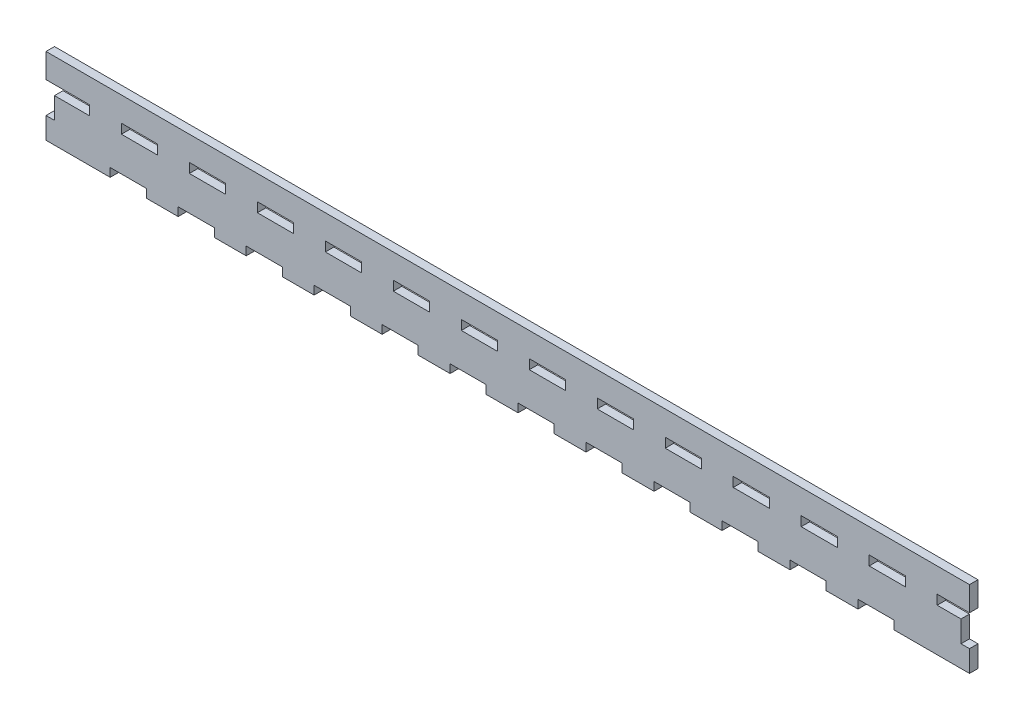
SolidWorks part; units mm, degrees
ref_plane "Plan de face" through (0, 0, 0) normal (0, 0, 1) x (1, 0, 0)
ref_plane "Plan de dessus" through (0, 0, 0) normal (0, 1, 0) x (1, 0, 0)
ref_plane "Plan de droite" through (0, 0, 0) normal (1, 0, 0) x (0, 0, -1)
sketch "Esquisse1" plane through (0, 0, 0) normal (0, 0, 1) x (1, 0, 0)
  line L6 (108.68, -6.055) -> (-108.68, -6.055)
  line L8 (108.68, -6.055) -> (108.68, 6.055)
  line L9 (108.68, 6.055) -> (-108.68, 6.055)
  line L10 (-108.68, -6.055) -> (-108.68, 6.055)
  point P4 (0, 0)
  point P5 (-108.8995, 6.2992)
extrude "Boss.-Extru.1" add sketch "Esquisse1" along normal blind 2
sketch "Esquisse2" plane through (0, 0, 0) normal (0, 0, -1) x (-1, 0, 0)
  line L0 (-108.68, 6.055) -> (-101.32, 6.055) construction
  line L1 (-109.57, 4.055) -> (-101.07, 4.055)
  line L2 (-109.57, 4.055) -> (-109.57, 6.305)
  line L3 (-109.57, 6.305) -> (-101.07, 6.305)
  line L4 (-101.07, 4.055) -> (-101.07, 6.305)
  line L9 (-93.32, 4.055) -> (-93.32, 6.055) construction
  line L10 (-101.32, 6.055) -> (-101.32, 4.055) construction
  line L12 (-85.07, 4.055) -> (-85.07, 6.305)
  line L13 (-93.57, 6.305) -> (-85.07, 6.305)
  line L14 (-93.57, 4.055) -> (-93.57, 6.305)
  line L15 (-93.57, 4.055) -> (-85.07, 4.055)
  line L16 (-69.07, 4.055) -> (-69.07, 6.305)
  line L17 (-77.57, 6.305) -> (-69.07, 6.305)
  line L18 (-77.57, 4.055) -> (-77.57, 6.305)
  line L19 (-77.57, 4.055) -> (-69.07, 4.055)
  line L20 (-53.07, 4.055) -> (-53.07, 6.305)
  line L21 (-61.57, 6.305) -> (-53.07, 6.305)
  line L22 (-61.57, 4.055) -> (-61.57, 6.305)
  line L23 (-61.57, 4.055) -> (-53.07, 4.055)
  line L24 (-37.07, 4.055) -> (-37.07, 6.305)
  line L25 (-45.57, 6.305) -> (-37.07, 6.305)
  line L26 (-45.57, 4.055) -> (-45.57, 6.305)
  line L27 (-45.57, 4.055) -> (-37.07, 4.055)
  line L28 (-21.07, 4.055) -> (-21.07, 6.305)
  line L29 (-29.57, 6.305) -> (-21.07, 6.305)
  line L30 (-29.57, 4.055) -> (-29.57, 6.305)
  line L31 (-29.57, 4.055) -> (-21.07, 4.055)
  line L32 (-5.07, 4.055) -> (-5.07, 6.305)
  line L33 (-13.57, 6.305) -> (-5.07, 6.305)
  line L34 (-13.57, 4.055) -> (-13.57, 6.305)
  line L35 (-13.57, 4.055) -> (-5.07, 4.055)
  line L36 (10.93, 4.055) -> (10.93, 6.305)
  line L37 (2.43, 6.305) -> (10.93, 6.305)
  line L38 (2.43, 4.055) -> (2.43, 6.305)
  line L39 (2.43, 4.055) -> (10.93, 4.055)
  line L40 (26.93, 4.055) -> (26.93, 6.305)
  line L41 (18.43, 6.305) -> (26.93, 6.305)
  line L42 (18.43, 4.055) -> (18.43, 6.305)
  line L43 (18.43, 4.055) -> (26.93, 4.055)
  line L44 (42.93, 4.055) -> (42.93, 6.305)
  line L45 (34.43, 6.305) -> (42.93, 6.305)
  line L46 (34.43, 4.055) -> (34.43, 6.305)
  line L47 (34.43, 4.055) -> (42.93, 4.055)
  line L48 (58.93, 4.055) -> (58.93, 6.305)
  line L49 (50.43, 6.305) -> (58.93, 6.305)
  line L50 (50.43, 4.055) -> (50.43, 6.305)
  line L51 (50.43, 4.055) -> (58.93, 4.055)
  line L52 (74.93, 4.055) -> (74.93, 6.305)
  line L53 (66.43, 6.305) -> (74.93, 6.305)
  line L54 (66.43, 4.055) -> (66.43, 6.305)
  line L55 (66.43, 4.055) -> (74.93, 4.055)
  line L56 (90.93, 4.055) -> (90.93, 6.305)
  line L57 (82.43, 6.305) -> (90.93, 6.305)
  line L58 (82.43, 4.055) -> (82.43, 6.305)
  line L59 (82.43, 4.055) -> (90.93, 4.055)
  line L60 (90.68, 6.055) -> (90.68, 4.055) construction
  line L61 (98.68, 4.055) -> (98.68, 6.055) construction
  line L62 (98.43, 4.055) -> (108.93, 4.055)
  line L63 (98.43, 4.055) -> (98.43, 6.305)
  line L64 (98.43, 6.305) -> (108.93, 6.305)
  line L65 (108.93, 4.055) -> (108.93, 6.305)
  line L66 (108.68, 6.055) -> (108.68, -6.055) construction
  line L68 (108.68, 6.055) -> (98.68, 6.055) construction
  line L70 (-90.93, -4.055) -> (-82.43, -4.055)
  line L71 (-90.93, -4.055) -> (-90.93, -6.305)
  line L72 (-90.93, -6.305) -> (-82.43, -6.305)
  line L73 (-82.43, -4.055) -> (-82.43, -6.305)
  line L74 (-90.68, -6.055) -> (-90.68, -4.055) construction
  line L75 (-90.68, -6.055) -> (-82.68, -6.055) construction
  line L76 (-82.68, -6.055) -> (-82.68, -4.055) construction
  line L77 (-74.93, -4.055) -> (-74.93, -6.305)
  line L78 (-74.93, -4.055) -> (-66.43, -4.055)
  line L79 (-66.43, -4.055) -> (-66.43, -6.305)
  line L80 (-74.93, -6.305) -> (-66.43, -6.305)
  line L81 (-58.93, -4.055) -> (-58.93, -6.305)
  line L82 (-58.93, -4.055) -> (-50.43, -4.055)
  line L83 (-50.43, -4.055) -> (-50.43, -6.305)
  line L84 (-58.93, -6.305) -> (-50.43, -6.305)
  line L85 (-42.93, -4.055) -> (-42.93, -6.305)
  line L86 (-42.93, -4.055) -> (-34.43, -4.055)
  line L87 (-34.43, -4.055) -> (-34.43, -6.305)
  line L88 (-42.93, -6.305) -> (-34.43, -6.305)
  line L89 (-26.93, -4.055) -> (-26.93, -6.305)
  line L90 (-26.93, -4.055) -> (-18.43, -4.055)
  line L91 (-18.43, -4.055) -> (-18.43, -6.305)
  line L92 (-26.93, -6.305) -> (-18.43, -6.305)
  line L93 (-10.93, -4.055) -> (-10.93, -6.305)
  line L94 (-10.93, -4.055) -> (-2.43, -4.055)
  line L95 (-2.43, -4.055) -> (-2.43, -6.305)
  line L96 (-10.93, -6.305) -> (-2.43, -6.305)
  line L97 (5.07, -4.055) -> (5.07, -6.305)
  line L98 (5.07, -4.055) -> (13.57, -4.055)
  line L99 (13.57, -4.055) -> (13.57, -6.305)
  line L100 (5.07, -6.305) -> (13.57, -6.305)
  line L101 (21.07, -4.055) -> (21.07, -6.305)
  line L102 (21.07, -4.055) -> (29.57, -4.055)
  line L103 (29.57, -4.055) -> (29.57, -6.305)
  line L104 (21.07, -6.305) -> (29.57, -6.305)
  line L105 (37.07, -4.055) -> (37.07, -6.305)
  line L106 (37.07, -4.055) -> (45.57, -4.055)
  line L107 (45.57, -4.055) -> (45.57, -6.305)
  line L108 (37.07, -6.305) -> (45.57, -6.305)
  line L109 (53.07, -4.055) -> (53.07, -6.305)
  line L110 (53.07, -4.055) -> (61.57, -4.055)
  line L111 (61.57, -4.055) -> (61.57, -6.305)
  line L112 (53.07, -6.305) -> (61.57, -6.305)
  line L113 (69.07, -4.055) -> (69.07, -6.305)
  line L114 (69.07, -4.055) -> (77.57, -4.055)
  line L115 (77.57, -4.055) -> (77.57, -6.305)
  line L116 (69.07, -6.305) -> (77.57, -6.305)
  line L117 (85.07, -4.055) -> (85.07, -6.305)
  line L118 (85.07, -4.055) -> (93.57, -4.055)
  line L119 (93.57, -4.055) -> (93.57, -6.305)
  line L120 (85.07, -6.305) -> (93.57, -6.305)
  line L121 (93.32, -6.055) -> (93.32, -4.055) construction
  line L122 (-101.32, 4.055) -> (-108.68, 4.055) construction
  line L123 (-90.68, -4.055) -> (-82.68, -4.055) construction
  dimension "D1" = 0.25
  dimension "D2" = 0.25
  dimension "D3" = 0.25
  dimension "D6" = 0.25
  dimension "D7" = 0.25
  dimension "D8" = 0.25
  dimension "D10" = 0.25
  dimension "D12" = 0.25
  dimension "D13" = 0.25
  dimension "D14" = 0.25
  dimension "D16" = 0.25
  dimension "D5" = 13
  dimension "D15" = 12
extrude "Enlèv. mat.-Extru.1" cut sketch "Esquisse2" against normal through all
sketch "Esquisse4" plane through (0, 0, 0) normal (0, 0, -1) x (-1, 0, 0)
  line L0 (106.68, -1) -> (108.68, -1) construction
  line L1 (106.68, 4.055) -> (108.68, 4.055)
  line L2 (106.68, 4.055) -> (106.68, -1)
  line L3 (106.68, -1) -> (108.68, -1)
  line L4 (108.68, 4.055) -> (108.68, -1)
  line L5 (106.68, 4.055) -> (106.68, -1) construction
extrude "Enlèv. mat.-Extru.2" cut sketch "Esquisse4" against normal through all
mirror "Symétrie1" about plane through (0, 0, 0) normal (1, 0, 0) of "Enlèv. mat.-Extru.2"
sketch "Esquisse5" plane through (0, 0, 0) normal (0, 0, -1) x (-1, 0, 0)
  line L0 (108.68, -1) -> (108.68, -6.055) construction
  line L1 (-108.68, 12.055) -> (108.68, 12.055)
  line L2 (-108.68, 12.055) -> (-108.68, 6.055)
  line L3 (-108.68, 6.055) -> (108.68, 6.055)
  line L4 (108.68, 12.055) -> (108.68, 6.055)
  line L5 (108.68, 12.055) -> (106.68, 12.055) construction
  line L6 (90.93, 6.055) -> (98.43, 6.055) construction
  line L7 (-108.68, 6.305) -> (-108.68, 12.055) construction
extrude "Boss.-Extru.2" add sketch "Esquisse5" against normal up to surface (2 mm away) up to face at (0.0489, 0.1131, 2)
sketch "Esquisse6" plane through (0, 0, 0) normal (0, 0, -1) x (-1, 0, 0)
  line L0 (-85.07, 4.055) -> (-85.07, 6.055) construction
  line L1 (-93.57, 6.055) -> (-85.07, 6.055)
  line L2 (-93.57, 6.055) -> (-93.57, 6.305)
  line L3 (-93.57, 6.305) -> (-85.07, 6.305)
  line L4 (-85.07, 6.055) -> (-85.07, 6.305)
  line L5 (-77.57, 6.055) -> (-69.07, 6.055)
  line L6 (-77.57, 6.055) -> (-77.57, 6.305)
  line L7 (-77.57, 6.305) -> (-69.07, 6.305)
  line L8 (-69.07, 6.055) -> (-69.07, 6.305)
  line L9 (-61.57, 6.055) -> (-53.07, 6.055)
  line L10 (-61.57, 6.055) -> (-61.57, 6.305)
  line L11 (-61.57, 6.305) -> (-53.07, 6.305)
  line L12 (-53.07, 6.055) -> (-53.07, 6.305)
  line L13 (-45.57, 6.055) -> (-37.07, 6.055)
  line L14 (-45.57, 6.055) -> (-45.57, 6.305)
  line L15 (-45.57, 6.305) -> (-37.07, 6.305)
  line L16 (-37.07, 6.055) -> (-37.07, 6.305)
  line L17 (-29.57, 6.055) -> (-21.07, 6.055)
  line L18 (-29.57, 6.055) -> (-29.57, 6.305)
  line L19 (-29.57, 6.305) -> (-21.07, 6.305)
  line L20 (-21.07, 6.055) -> (-21.07, 6.305)
  line L21 (-13.57, 6.055) -> (-5.07, 6.055)
  line L22 (-13.57, 6.055) -> (-13.57, 6.305)
  line L23 (-13.57, 6.305) -> (-5.07, 6.305)
  line L24 (-5.07, 6.055) -> (-5.07, 6.305)
  line L25 (2.43, 6.055) -> (10.93, 6.055)
  line L26 (2.43, 6.055) -> (2.43, 6.305)
  line L27 (2.43, 6.305) -> (10.93, 6.305)
  line L28 (10.93, 6.055) -> (10.93, 6.305)
  line L29 (18.43, 6.055) -> (26.93, 6.055)
  line L30 (18.43, 6.055) -> (18.43, 6.305)
  line L31 (18.43, 6.305) -> (26.93, 6.305)
  line L32 (26.93, 6.055) -> (26.93, 6.305)
  line L33 (34.43, 6.055) -> (42.93, 6.055)
  line L34 (34.43, 6.055) -> (34.43, 6.305)
  line L35 (34.43, 6.305) -> (42.93, 6.305)
  line L36 (42.93, 6.055) -> (42.93, 6.305)
  line L37 (50.43, 6.055) -> (58.93, 6.055)
  line L38 (50.43, 6.055) -> (50.43, 6.305)
  line L39 (50.43, 6.305) -> (58.93, 6.305)
  line L40 (58.93, 6.055) -> (58.93, 6.305)
  line L41 (66.43, 6.055) -> (74.93, 6.055)
  line L42 (66.43, 6.055) -> (66.43, 6.305)
  line L43 (66.43, 6.305) -> (74.93, 6.305)
  line L44 (74.93, 6.055) -> (74.93, 6.305)
  line L45 (82.43, 6.055) -> (90.93, 6.055)
  line L46 (82.43, 6.055) -> (82.43, 6.305)
  line L47 (82.43, 6.305) -> (90.93, 6.305)
  line L48 (90.93, 6.055) -> (90.93, 6.305)
  line L53 (98.43, 6.055) -> (106.93, 6.055) [skipped]
  line L54 (98.43, 6.055) -> (98.43, 6.305) [skipped]
  line L55 (98.43, 6.305) -> (106.93, 6.305) [skipped]
  line L56 (106.93, 6.055) -> (106.93, 6.305) [skipped]
  line L57 (90.93, 4.055) -> (90.93, 6.055) construction
  line L58 (108.68, 6.055) -> (108.68, 12.055) construction
  line L59 (98.43, 6.055) -> (108.68, 6.055)
  line L60 (98.43, 6.055) -> (98.43, 6.305)
  line L61 (98.43, 6.305) -> (108.68, 6.305)
  line L62 (108.68, 6.055) -> (108.68, 6.305)
  line L63 (-108.68, 12.055) -> (-108.68, 6.055) construction
  line L64 (-101.07, 6.055) -> (-108.68, 6.055)
  line L65 (-101.07, 6.055) -> (-101.07, 6.305)
  line L66 (-101.07, 6.305) -> (-108.68, 6.305)
  line L67 (-108.68, 6.055) -> (-108.68, 6.305)
  dimension "D1" = 0.25
  dimension "D2" = 13
extrude "Enlèv. mat.-Extru.3" cut sketch "Esquisse6" against normal through all
